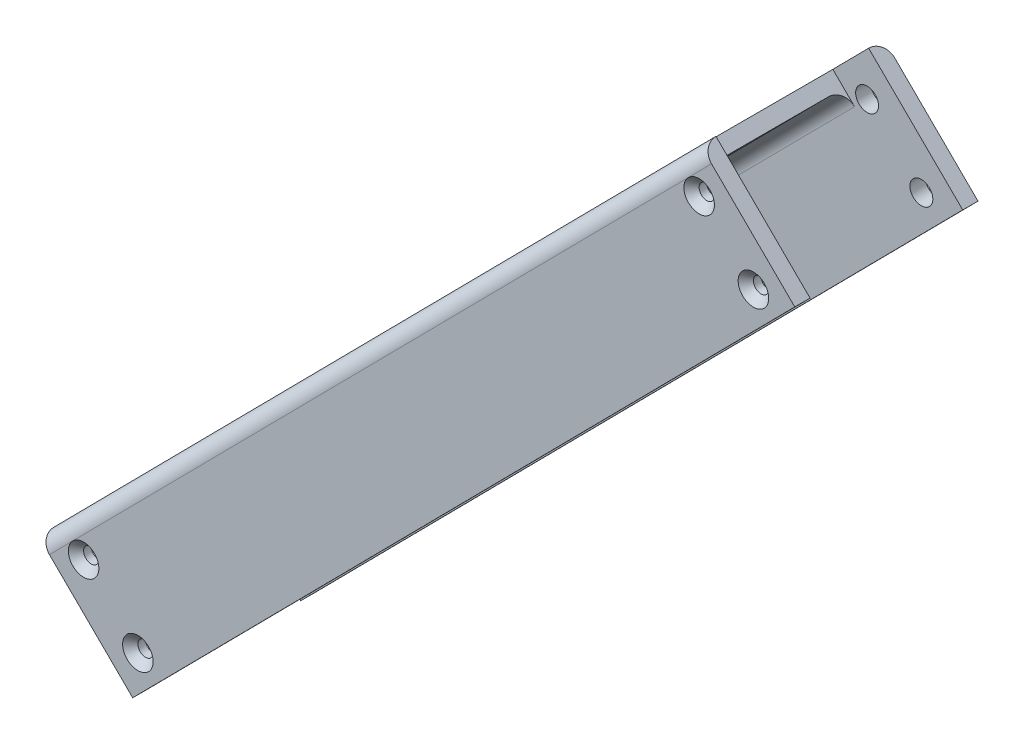
SolidWorks part; units mm, degrees
ref_plane "Front Plane" through (0, 0, 0) normal (0, 0, 1) x (1, 0, 0)
ref_plane "Top Plane" through (0, 0, 0) normal (0, 1, 0) x (1, 0, 0)
ref_plane "Right Plane" through (0, 0, 0) normal (1, 0, 0) x (0, 0, -1)
sketch "Sketch2" plane through (0, 0, 0) normal (0, 0, 1) x (1, 0, 0)
  line L0 (165.715, 148.457) -> (35.6364, 16.9102)
  line L1 (35.6364, 16.9102) -> (54.1241, -1.3711)
  line L4 (54.1241, -1.3711) -> (184.2027, 130.1757)
  line L25 (165.715, 148.457) -> (184.2027, 130.1757)
extrude "Boss-Extrude1" add sketch "Sketch2" against normal blind 3
sketch "Sketch4" plane through (0, 0, -36) normal (0, 0, -1) x (-1, 0, 0)
  line L6 (-165.715, 148.457) -> (-184.2027, 130.1757)
  line L9 (-184.2027, 130.1757) -> (-54.1241, -1.3711)
  line L10 (-54.1241, -1.3711) -> (-35.6364, 16.9102)
  line L11 (-35.6364, 16.9102) -> (-165.715, 148.457)
  line L12 (-165.715, 148.457) -> (-184.2027, 130.1757)
  line L15 (-184.2027, 130.1757) -> (-54.1241, -1.3711)
  line L16 (-54.1241, -1.3711) -> (-35.6364, 16.9102)
  line L17 (-35.6364, 16.9102) -> (-165.715, 148.457)
  dimension "D1" = 0
extrude "Boss-Extrude2" add sketch "Sketch4" against normal blind 3 separate body
sketch "Sketch5" plane through (0, 0, -3) normal (0, 0, -1) x (-1, 0, 0)
  line L0 (-35.6364, 16.9102) -> (-165.715, 148.457) construction
  line L1 (-35.6364, 16.9102) -> (-165.715, 148.457)
  line L2 (-37.7696, 14.8008) -> (-167.8482, 146.3476)
  line L3 (-37.7696, 14.8008) -> (-35.6364, 16.9102)
  line L4 (-167.8482, 146.3476) -> (-165.715, 148.457)
  dimension "D1" = 3
extrude "Boss-Extrude3" add sketch "Sketch5" along normal up to surface (30 mm away) up to face at (109.9195, 73.543, -33)
fillet "Fillet1" radius 3 4 edges at (102.8089, 80.5742, -3) (102.8089, 80.5742, -33) (100.6757, 82.6836, -36) (100.6757, 82.6836, 0)
sketch "Sketch6" plane through (9.5636, -9.4569, 0) normal (-0.7111, 0.7031, 0) x (0, 0, 1)
  circle A0 centre (-18, 197.0812) radius 7.5
extrude "Cut-Extrude1" cut sketch "Sketch6" against normal up to surface (3 mm away) up to face at (102.8089, 80.5742, -18)
sketch "Sketch7" plane through (9.5636, -9.4569, 0) normal (-0.7111, 0.7031, 0) x (0, 0, 1)
  line L5 (-3, 37.0812) -> (-3, 222.0812) construction
  line L6 (-3, 212.0812) -> (-3, 222.0812)
  line L7 (-33, 222.0812) -> (-33, 37.0812) construction
  line L8 (-33, 222.0812) -> (-33, 212.0812)
  line L9 (-33, 212.0812) -> (-3, 212.0812)
  line L12 (-33, 222.0812) -> (-3, 222.0812)
  line L13 (-36, 129.5812) -> (0, 129.5812) construction
  line L14 (-36, 37.0812) -> (-36, 222.0812) construction
  line L15 (0, 222.0812) -> (0, 37.0812) construction
  line L16 (-33, 37.0812) -> (-3, 37.0812)
  line L17 (-33, 47.0812) -> (-3, 47.0812)
  line L18 (-33, 37.0812) -> (-33, 47.0812)
  line L19 (-3, 47.0812) -> (-3, 37.0812)
extrude "Cut-Extrude2" cut sketch "Sketch7" against normal up to surface (26 mm away) up to face at (119.1634, 64.4023, -1.5)
sketch "Sketch8" plane through (0, 0, 0) normal (0, 0, 1) x (1, 0, 0)
  line L0 (58.6944, 3.2508) -> (40.2067, 21.5321) construction
  line L5 (179.6323, 125.5538) -> (161.1447, 143.8351) construction
  line L6 (158.6837, 141.3464) -> (165.715, 148.457) construction
  line L8 (100.6757, 82.6836) -> (119.1634, 64.4023) construction
  line L9 (42.6677, 24.0208) -> (158.6837, 141.3464) construction
  line L10 (54.1241, -1.3711) -> (184.2027, 130.1757) construction
  circle A0 centre (176.077, 129.0694) radius 1.5
  circle A1 centre (165.4111, 139.6163) radius 1.5
  circle A2 centre (44.4731, 17.3134) radius 1.5
  circle A3 centre (55.1391, 6.7664) radius 1.5
extrude "Cut-Extrude3" cut sketch "Sketch8" against normal blind 3
sketch "Sketch9" plane through (0, 0, -36) normal (0, 0, -1) x (-1, 0, 0)
  circle A0 centre (-165.4111, 139.6163) radius 2.25
  circle A1 centre (-176.077, 129.0694) radius 2.25
  circle A2 centre (-44.4731, 17.3134) radius 2.25
  circle A3 centre (-55.1391, 6.7664) radius 2.25
extrude "Cut-Extrude4" cut sketch "Sketch9" against normal blind 3
chamfer "Chamfer1" distance 1.5 angle 45 4 edges at (42.9731, 17.3134, 0) (53.6391, 6.7664, 0) (177.577, 129.0694, 0) (166.9111, 139.6163, 0)
